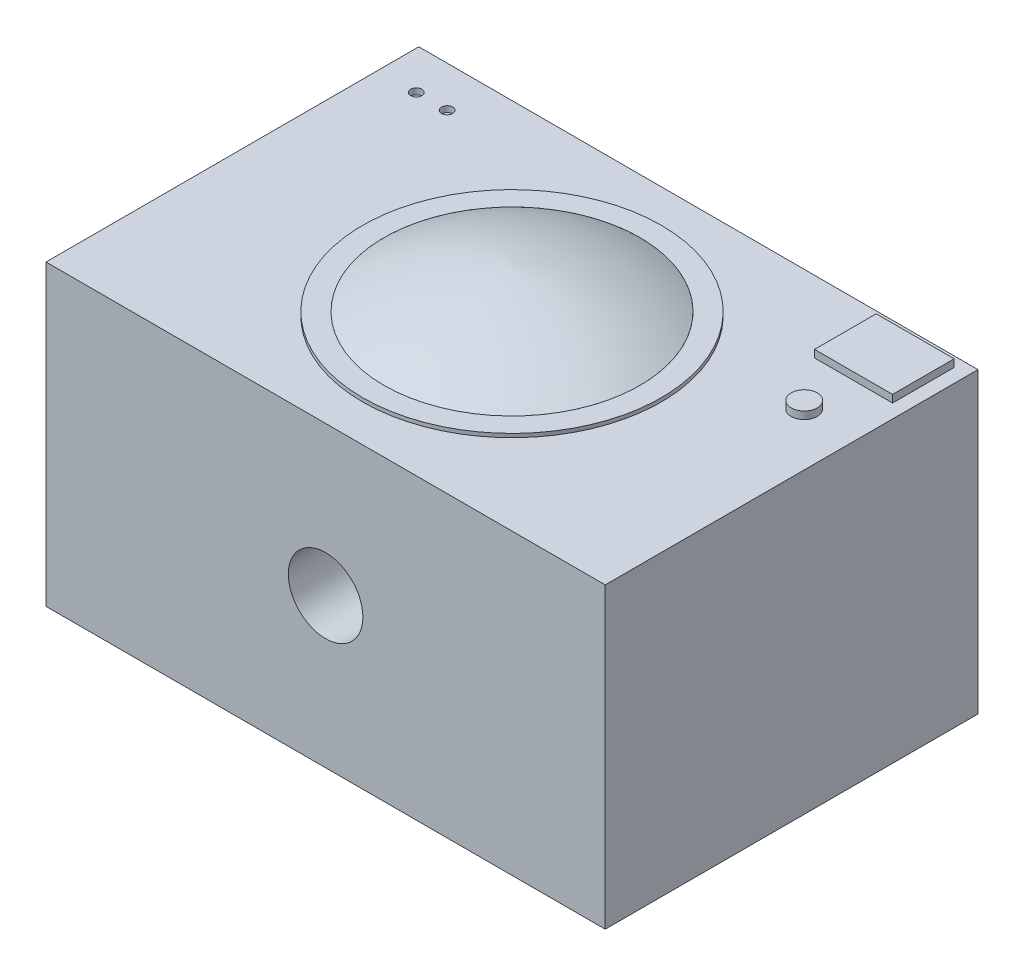
SolidWorks part; units mm, degrees
ref_plane "Front Plane" through (0, 0, 0) normal (0, 0, 1) x (1, 0, 0)
ref_plane "Top Plane" through (0, 0, 0) normal (0, 1, 0) x (1, 0, 0)
ref_plane "Right Plane" through (0, 0, 0) normal (1, 0, 0) x (0, 0, -1)
sketch "Sketch1" plane through (0, 0, 0) normal (0, 1, 0) x (1, 0, 0)
  line L1 (-37.5, 25) -> (37.5, 25)
  line L2 (-37.5, 25) -> (-37.5, -25)
  line L3 (-37.5, -25) -> (37.5, -25)
  line L4 (37.5, 25) -> (37.5, -25)
  line L5 (-37.5, 25) -> (37.5, -25) construction
  line L6 (-37.5, -25) -> (37.5, 25) construction
  point P0 (0, 0)
  dimension "D1" = 75
  dimension "D2" = 50
extrude "Boss-Extrude1" add sketch "Sketch1" along normal blind 40
sketch "Sketch2" plane through (0, 40, 0) normal (0, 1, 0) x (1, 0, 0)
  circle A0 centre (0, 0) radius 20.0266
  circle A1 centre (0, 0) radius 17.167
extrude "Boss-Extrude2" add sketch "Sketch2" along normal blind 0.5
sketch "Sketch3" plane through (0, 0, 0) normal (0, 0, 1) x (1, 0, 0)
  line L0 (0, 40) -> (0, 45.6413)
  line L1 (-37.5, 40) -> (37.5, 40) construction
  line L2 (0, 40) -> (17.167, 40.5)
  arc A0 (17.167, 40.5) -> (0, 45.6413) centre (-2.6567, 5.5387) ccw
revolve "Revolve1" add sketch "Sketch3" angle 360 about L0
sketch "Sketch4" plane through (0, 40, 0) normal (0, 1, 0) x (1, 0, 0)
  line L1 (25.1848, 15.3907) -> (35.6481, 15.3907)
  line L2 (25.1848, 15.3907) -> (25.1848, 23.664)
  line L3 (25.1848, 23.664) -> (35.6481, 23.664)
  line L4 (35.6481, 15.3907) -> (35.6481, 23.664)
  line L5 (25.1848, 15.3907) -> (35.6481, 23.664) construction
  line L6 (25.1848, 23.664) -> (35.6481, 15.3907) construction
  circle A0 centre (30.4165, 8.7743) radius 1.75
  circle A1 centre (-32.3631, 19.5274) radius 0.75
  circle A2 centre (-28.2265, 19.5274) radius 0.75
  point P0 (30.4165, 19.5274)
  dimension "D1" = 1.5
  dimension "D2" = 1.5
  dimension "D3" = 3.5
extrude "Boss-Extrude3" add sketch "Sketch4" along normal blind 1 contours L1 L4 L3 L2 | A0 region at (30.4165, 40, -19.5274) region at (30.4165, 40, -8.7743)
extrude "Cut-Extrude1" cut sketch "Sketch4<3>" against normal blind 0.8 contours A1 | A2 region at (-32.3631, 40, -19.5274) region at (-28.2265, 40, -19.5274)
sketch "Sketch4<3>" plane through (0, 40, 0) normal (0, 1, 0) x (1, 0, 0) same geometry as "Sketch4"
sketch "Sketch5" plane through (0, 0, 0) normal (0, -1, 0) x (1, 0, 0)
  line L1 (-34.5523, -15.7958) -> (34.5523, -15.7958)
  line L2 (-34.5523, -15.7958) -> (-34.5523, 15.7958)
  line L3 (-34.5523, 15.7958) -> (34.5523, 15.7958)
  line L4 (34.5523, -15.7958) -> (34.5523, 15.7958)
  line L5 (-34.5523, -15.7958) -> (34.5523, 15.7958) construction
  line L6 (-34.5523, 15.7958) -> (34.5523, -15.7958) construction
  point P0 (0, 0)
extrude "Cut-Extrude2" cut sketch "Sketch5" against normal blind 0.3
sketch "Sketch6" plane through (0, 0, -25) normal (0, 0, -1) x (-1, 0, 0)
  line L1 (-36.7431, 5.2399) -> (36.7431, 5.2399)
  line L2 (-36.7431, 5.2399) -> (-36.7431, 6.2132)
  line L3 (-36.7431, 6.2132) -> (36.7431, 6.2132)
  line L4 (36.7431, 5.2399) -> (36.7431, 6.2132)
  line L5 (-36.7431, 5.2399) -> (36.7431, 6.2132) construction
  line L6 (-36.7431, 6.2132) -> (36.7431, 5.2399) construction
  line L7 (-34.2807, 6.9328) -> (-15.3505, 6.9328)
  line L8 (-34.2807, 6.9328) -> (-34.2807, 14.9362)
  line L9 (-34.2807, 14.9362) -> (-15.3505, 14.9362)
  line L10 (-15.3505, 6.9328) -> (-15.3505, 14.9362)
  point P0 (0, 5.7266)
extrude "Cut-Extrude3" cut sketch "Sketch6" against normal blind 0.3
sketch "Sketch7" plane through (-37.5, 0, 0) normal (-1, 0, 0) x (0, 0, 1)
  line L1 (-23.6666, 25.4556) -> (23.475, 25.4556)
  line L2 (-23.6666, 25.4556) -> (-23.6666, 12.9995)
  line L3 (-23.6666, 12.9995) -> (23.475, 12.9995)
  line L4 (23.475, 25.4556) -> (23.475, 12.9995)
extrude "Cut-Extrude4" cut sketch "Sketch7" against normal blind 0.3
sketch "Sketch8" plane through (0, 0, 25) normal (0, 0, 1) x (1, 0, 0)
  line L0 (37.5, 40) -> (-37.5, 0) construction
  line L1 (-37.5, 0) -> (37.5, 0) construction
  circle A0 centre (0, 20) radius 5
  dimension "D1" = 10
extrude "Cut-Extrude5" cut sketch "Sketch8" against normal blind 10
